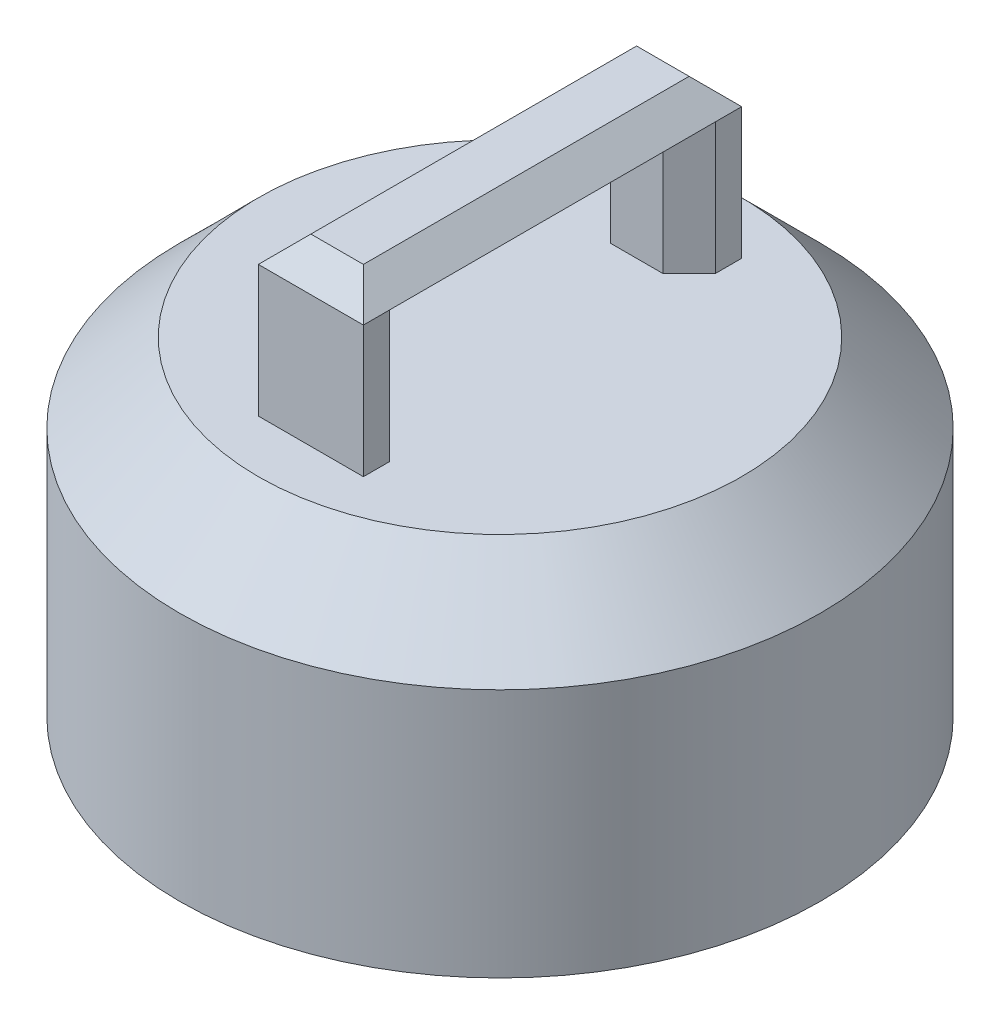
SolidWorks part; units mm, degrees
ref_plane "Alzado" through (0, 0, 0) normal (0, 0, 1) x (1, 0, 0)
ref_plane "Planta" through (0, 0, 0) normal (0, 1, 0) x (1, 0, 0)
ref_plane "Vista lateral" through (0, 0, 0) normal (1, 0, 0) x (0, 0, -1)
sketch "Croquis1" plane through (0, 0, 0) normal (0, 0, 1) x (1, 0, 0)
  line L0 (0, -12.6252) -> (0, 19.4103) construction
  line L2 (0, 16.3748) -> (12.2, 16.3748)
  line L3 (0, 16.3748) -> (0, 14.3748)
  line L4 (0, 14.3748) -> (10.2, 14.3748)
  line L7 (12.2, 16.3748) -> (12.2, 2.8748)
  line L8 (12.2, 2.8748) -> (10.2, 2.8748)
  line L9 (10.2, 14.3748) -> (10.2, 2.8748)
  dimension "D1" = 13.5
  dimension "D2" = 10.2
  dimension "D3" = 2
  dimension "D4" = 2
revolve "Revolución1" add sketch "Croquis1" angle 360 about L0
chamfer "Chaflán1" distance 3 angle 45 2 edges at (0, 2.8748, -10.2) (0, 16.3748, -12.2)
thread "Rosca1" pitch 1.5 method extrude profile "Perfil de rosca1" start angle 0, offset 0, length 5.5, pitch 1.5, diameter 20.4
ref_plane "Plano1" through (10.2, 5.8748, 0) normal (0, 0, 1) x (1, 0, 0)
sketch "Perfil de rosca1" plane through (10.2, 5.8748, 0) normal (0, 0, 1) x (1, 0, 0)
  line L0 (0, 0) -> (0, 1.5) construction
  line L11 (0, 0) -> (0, 1.3125)
  line L12 (0, 1.3125) -> (-0.8119, 0.8437)
  line L13 (-0.8119, 0.8437) -> (-0.8119, 0.4687)
  line L15 (-0.8119, 0.4687) -> (0, 0)
  line L17 (-0.8119, 0.6562) -> (0, 0.6562) construction
  point P2 (0, 0)
  dimension "Pitch" = 1.5
  dimension "Profile_Angle" = 60
  dimension "Profile_Land" = 0.375
  dimension "Profile_Height" = 0.8119
sketch "Croquis2" plane through (0, 0, 0) normal (1, 0, 0) x (0, 0, -1)
  line L0 (9.2, 16.3748) -> (-9.2, 16.3748) construction
  line L1 (-7.2, 16.3748) -> (-5.2, 16.3748)
  line L2 (-7.2, 16.3748) -> (-7.2, 22.3748)
  line L4 (-5.2, 16.3748) -> (-5.2, 20.3748)
  line L6 (-7.2, 22.3748) -> (7.2, 22.3748)
  line L8 (-5.2, 20.3748) -> (5.2, 20.3748)
  line L11 (7.2, 22.3748) -> (7.2, 16.3748)
  line L12 (7.2, 16.3748) -> (5.2, 16.3748)
  line L13 (5.2, 20.3748) -> (5.2, 16.3748)
  dimension "D1" = 2
  dimension "D2" = 2
  dimension "D3" = 2
  dimension "D4" = 2
  dimension "D5" = 2
  dimension "D6" = 4
extrude "Saliente-Extruir1" add sketch "Croquis2" along normal mid plane 4
chamfer "Chaflán2" distance 1 angle 45 4 edges at (0, 22.3748, -7.2) (2, 22.3748, 0) (0, 22.3748, 7.2) (-2, 22.3748, 0)
chamfer "Chaflán3" distance 1 angle 45 6 edges at (2, 18.3748, -5.2) (2, 18.3748, 5.2) (2, 20.3748, 0) (-2, 18.3748, -5.2) (-2, 18.3748, 5.2) (-2, 20.3748, 0)
